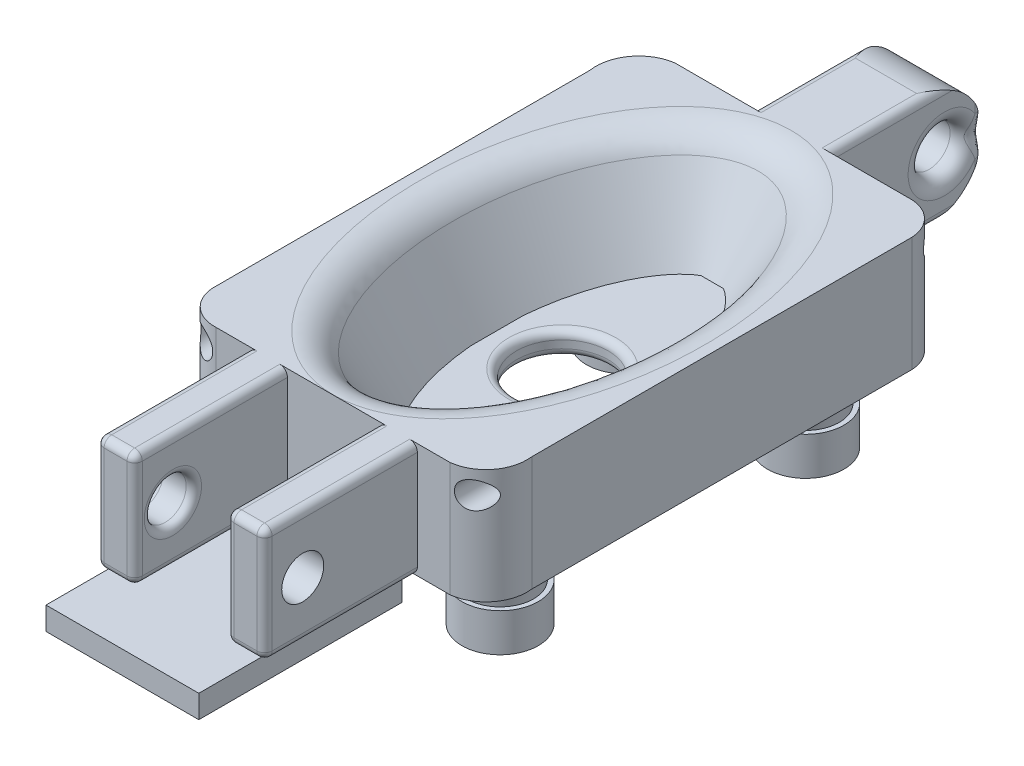
SolidWorks part; units mm, degrees
ref_plane "Front Plane" through (0, 0, 0) normal (0, 0, 1) x (1, 0, 0)
ref_plane "Top Plane" through (0, 0, 0) normal (0, 1, 0) x (1, 0, 0)
ref_plane "Right Plane" through (0, 0, 0) normal (1, 0, 0) x (0, 0, -1)
sketch "Sketch1" plane through (0, 0, 0) normal (0, 1, 0) x (1, 0, 0)
  line L1 (-15.3125, -30) -> (15.3125, -30)
  line L2 (-20, -25.7813) -> (-20, 23.5937)
  line L3 (-15.3125, 30) -> (15.3125, 30)
  line L4 (20, -24.0015) -> (20, 25.7812)
  line L5 (-20, -30) -> (20, 30) construction
  line L6 (-20, 30) -> (20, -30) construction
  arc A0 (-15.3125, 30) -> (-20, 23.5937) centre (-14.4531, 24.4531) ccw
  arc A1 (15.3125, 30) -> (20, 25.7812) centre (15.5469, 25.5469) cw
  arc A2 (15.3125, -30) -> (20, -24.0015) centre (14.657, -24.657) ccw
  arc A3 (-15.3125, -30) -> (-20, -25.7813) centre (-15.5469, -25.5469) cw
  point P0 (0, 0)
  dimension "D1" = 40
  dimension "D2" = 60
extrude "Boss-Extrude1" add sketch "Sketch1" along normal blind 15
sketch "Sketch2" plane through (0, 0, 30) normal (0, 0, 1) x (1, 0, 0)
  line L0 (-20, 15) -> (-20, 0) construction
  line L1 (20.0401, 0) -> (20.0401, 15) construction
  line L2 (15.3125, 0) -> (20.0401, 0) construction
  line L3 (-20, 0) -> (-15.3125, 0) construction
  circle A0 centre (-17.5, 12) radius 1.75
  circle A1 centre (17.5401, 12) radius 1.75
  dimension "D1" = 2.5
  dimension "D5" = 3.5
  dimension "D6" = 3.5
  dimension "D2" = 2.5
  dimension "D3" = 12
  dimension "D4" = 12
sketch "Sketch4" plane through (0, 15, 0) normal (0, 1, 0) x (1, 0, 0)
  ellipse E0 centre (0, 0) end of major axis (0, 27.1105) minor radius 15.7856
extrude "Cut-Extrude6" cut sketch "Sketch4" against normal blind 15 draft 30.5
fillet "Fillet4" radius 5 1 edges at (-2.7969, 15, -26.6816) type face fillet first side face at (-0.082, 0, -18.2666) second side face at (-2.7969, 15, -26.6816)
extrude "Cut-Extrude7" cut sketch "Sketch2" against normal blind 150
sketch "Sketch5" plane through (0, 0, 0) normal (0, -1, 0) x (1, 0, 0)
  line L1 (7.7139, -19.6019) -> (-8.5645, -19.6019)
  line L2 (7.7139, -19.6019) -> (7.7139, 20.1727)
  line L3 (7.7139, 20.1727) -> (-8.5645, 20.1727)
  line L4 (-8.5645, -19.6019) -> (-8.5645, 20.1727)
extrude "Boss-Extrude2" add sketch "Sketch5" against normal blind 3
sketch "Sketch6" plane through (0, 3, 0) normal (0, 1, 0) x (1, 0, 0)
  circle A0 centre (0, 0) radius 6
extrude "Cut-Extrude8" cut sketch "Sketch6" against normal blind 3
sketch "Sketch8" plane through (0, 0, -30) normal (0, 0, -1) x (-1, 0, 0)
  line L7 (-5, 15) -> (5, 15)
  line L8 (-5, 15) -> (-5, 0)
  line L9 (-5, 0) -> (5, 0)
  line L10 (5, 15) -> (5, 0)
  point P9 (0, 7.5)
extrude "Boss-Extrude3" add sketch "Sketch8" along normal blind 20
sketch "Sketch10" plane through (-5, 0, 0) normal (-1, 0, 0) x (0, 0, 1)
  line L0 (-50, 0) -> (-50, 15) construction
  line L1 (-50, 15) -> (-30, 15) construction
  circle A0 centre (-45, 7.32) radius 2.75
  dimension "D1" = 5
  dimension "D3" = 5.5
  dimension "D2" = 7.68
extrude "Cut-Extrude9" cut sketch "Sketch10" against normal blind 20
fillet "Fillet8" radius 2 1 edges at (5, 4.57, -45) type face fillet first side face at (5, 4.57, -45) second side face at (-5, 4.57, -45)
fillet "Fillet9" radius 1 1 edges at (-5, 4.57, -45) type face fillet first side face at (-5, 4.57, -45) second side face at (3, 4.57, -45)
fillet "Fillet11" radius 1 1 edges at (0, 15, -50) type face fillet first side face at (0, 7.5, -50) second side face at (-1.6146, 15, 29.8598)
fillet "Fillet12" radius 1 1 edges at (-5, 15, -39.5) type face fillet first side face at (-5, 11.07, -45) second side face at (-1.6146, 15, 29.8598)
fillet "Fillet13" radius 1 1 edges at (5, 15, -39.5) type face fillet first side face at (5, 2.57, -45) second side face at (-1.6146, 15, 29.8598)
fillet "Fillet14" radius 1 1 edges at (5, 0, -39.5) type face fillet first side face at (0, 0, 6) second side face at (5, 7.1067, -41.2083)
sketch "Sketch11" plane through (0, 0, 30) normal (0, 0, 1) x (1, 0, 0)
  line L3 (-10.98, 0) -> (-5.98, 0)
  line L10 (6.02, 0) -> (11.02, 0)
  line L15 (-5.98, 15) -> (-5.98, 0)
  line L20 (6.02, 15) -> (6.02, 0)
  line L25 (6.02, 0) -> (11.02, 0)
  line L26 (6.02, 0) -> (6.02, 15)
  line L27 (6.02, 15) -> (11.02, 15)
  line L28 (11.02, 0) -> (11.02, 15)
  line L30 (-5.98, 15) -> (-10.98, 15)
  line L31 (-5.98, 15) -> (-5.98, 0)
  line L32 (-5.98, 0) -> (-10.98, 0)
  line L33 (-10.98, 15) -> (-10.98, 0)
  point P7 (0.02, 7.5)
  line M22 (-15.3125, 0) -> (15.3125, 0)
  line M24 (15.3125, 15) -> (-15.3125, 15)
  dimension "D7" = 5
extrude "Boss-Extrude4" add sketch "Sketch11" along normal blind 20 contours L33 L15 M24 M22 | L28 L20 M22 M24 region at (-8.48, 7.5, 30) region at (8.52, 7.5, 30)
sketch "Sketch12" plane through (-10.98, 0, 0) normal (-1, 0, 0) x (0, 0, 1)
  line L0 (50, 0) -> (50, 15) construction
  line L1 (50, 15) -> (30, 15) construction
  circle A0 centre (45, 7.32) radius 2.75
  dimension "D1" = 5
  dimension "D3" = 5.5
  dimension "D2" = 7.68
extrude "Cut-Extrude10" cut sketch "Sketch12" against normal blind 250
fillet "Fillet17" radius 1 1 edges at (-10.98, 4.57, 45) type face fillet first side face at (-5.98, 7.32, 42.25) second side face at (-10.98, 4.57, 45)
fillet "Fillet18" radius 1 1 edges at (-5.98, 7.32, 42.25) type face fillet first side face at (-9.98, 10.07, 45) second side face at (-5.98, 7.32, 42.25)
fillet "Fillet19" radius 1 1 edges at (-5.98, 0, 40) type face fillet first side face at (-5.98, 7.32, 41.25) second side face at (0, 0, 6)
fillet "Fillet20" radius 1 1 edges at (-8.98, 0, 50) type face fillet first side face at (0, 0, 6) second side face at (-8.1386, 6.1586, 50)
fillet "Fillet21" radius 1 1 edges at (-10.98, 0, 39.5) type face fillet first side face at (-10.98, 11.07, 45) second side face at (0, 0, 6)
fillet "Fillet22" radius 1 1 edges at (-5.98, 15, 39.5) type face fillet first side face at (-1.6146, 15, 29.8598) second side face at (-5.98, 7.32, 41.25)
fillet "Fillet23" radius 1 1 edges at (6.02, 0, 40) type face fillet first side face at (6.02, 7.32, 42.25) second side face at (0, 0, 6)
fillet "Fillet25" radius 1 1 edges at (9.02, 0, 50) type face fillet first side face at (0, 0, 6) second side face at (8.1786, 6.1586, 50)
fillet "Fillet26" radius 1 1 edges at (11.02, 0, 39.5) type face fillet first side face at (0, 0, 6) second side face at (11.02, 7.32, 47.75)
fillet "Fillet27" radius 1 1 edges at (11.02, 15, 39.5) type face fillet first side face at (-1.6146, 15, 29.8598) second side face at (11.02, 7.32, 47.75)
fillet "Fillet28" radius 1 1 edges at (6.02, 7.32, 42.25) type face fillet first side face at (6.02, 7.32, 42.25) second side face at (6.02, 7.32, 42.25)
fillet "Fillet29" radius 1 1 edges at (0, 0, 6) type face fillet first side face at (0, 0, 6) second side face at (0, 0, 6)
fillet "Fillet30" radius 1 1 edges at (0, 3, 6) type face fillet first side face at (0, 3, 6) second side face at (0, 1, 6)
sketch "Sketch13" plane through (0, 0, 0) normal (0, -1, 0) x (1, 0, 0)
  line L0 (-20, -23.5937) -> (-20, 25.7813) construction
  line L1 (20, 24.0015) -> (20, -25.7812) construction
  circle A0 centre (-11.8492, 20) radius 5
  circle A1 centre (11.85, 20) radius 5
  circle A2 centre (-11.8492, -20) radius 5
  circle A3 centre (11.85, -20) radius 5
  dimension "D1" = 10
  dimension "D4" = 10
  dimension "D7" = 10
  dimension "D8" = 10
  dimension "D2" = 8.1508
  dimension "D3" = 20
  dimension "D5" = 8.15
  dimension "D6" = 20
  dimension "D9" = 8.1508
  dimension "D10" = 8.15
  dimension "D11" = 20
  dimension "D12" = 20
extrude "Boss-Extrude5" add sketch "Sketch13" along normal blind 5 draft 7
sketch "Sketch14" plane through (0, -5, 0) normal (0, -1, 0) x (1, 0, 0)
  circle A0 centre (-11.8492, 20) radius 5
  circle A1 centre (11.85, 20) radius 5
  circle A2 centre (11.85, -20) radius 5
  circle A3 centre (-11.8492, -20) radius 5
  dimension "D1" = 10
  dimension "D2" = 10
  dimension "D3" = 10
  dimension "D4" = 10
extrude "Boss-Extrude6" add sketch "Sketch14" along normal blind 5
sketch "Sketch19" plane through (0, 0, 0) normal (0, -1, 0) x (1, 0, 0)
  line L0 (10.02, 30) -> (10.02, 49) construction
  line L2 (-9.98, 49) -> (-9.98, 31)
  line L3 (-9.98, 31) -> (10.02, 31)
  line L4 (10.02, 49) -> (10.02, 31)
  line L8 (10.02, 49) -> (10.02, 57.6029)
  line L9 (10.02, 57.6029) -> (-9.98, 57.6029)
  line L10 (-9.98, 49) -> (-9.98, 57.6029)
  dimension "D1" = 18
extrude "Boss-Extrude14" add sketch "Sketch19" along normal blind 3
sketch "Sketch24" plane through (-5, 0, 0) normal (-1, 0, 0) x (0, 0, 1)
  line L0 (-49, 15) -> (-30, 15) construction
  line L1 (-30, 0) -> (-49, 0) construction
  line L3 (-42.0784, 15) -> (-50.6216, 15)
  line L5 (-42.0784, -0.0041) -> (-50.6216, -0.0041)
  line L6 (-50.6216, 15) -> (-50.6216, -0.0041)
  arc A1 (-50.0388, 7.32) -> (-42.0784, 15) centre (-42.2186, 7.1798) cw
  arc A2 (-42.2186, 0) -> (-50.0388, 7.32) centre (-42.4687, 7.5701) cw
  line M3 (-49, 14) -> (-49, 1)
  line M4 (-49, 1) -> (-30, 1)
  line M6 (-30, 14) -> (-49, 14)
  dimension "D1" = 8.5432
extrude "Cut-Extrude11" cut sketch "Sketch24" against normal blind 25 contours A1 M3 M6 | A2 A1 L3 L6 L5 M3 M6 M4 | A2 M4 M3 region at (-5, 14.8941, -44.3099) region at (-5, 13.1156, -48.107) region at (-5, 1.8304, -48.1614)
